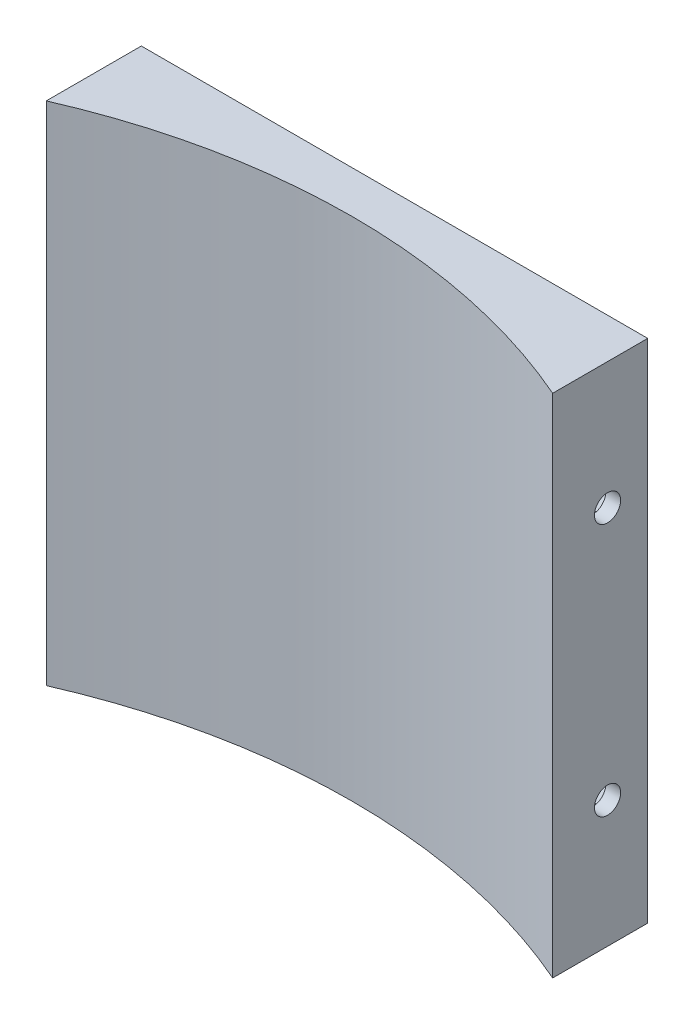
SolidWorks part; units mm, degrees
ref_plane "Plano frontal" through (0, 0, 0) normal (0, 0, 1) x (1, 0, 0)
ref_plane "Plano superior" through (0, 0, 0) normal (0, 1, 0) x (1, 0, 0)
ref_plane "Plano direito" through (0, 0, 0) normal (1, 0, 0) x (0, 0, -1)
sketch "Esboço2" plane through (0, 0, 0) normal (0, 1, 0) x (1, 0, 0)
  line L0 (-60, 0) -> (60, 0)
  line L1 (-60, -22.5227) -> (-60, 0)
  line L2 (60, 0) -> (60, -22.5227)
  arc A0 (-60, -22.5227) -> (60, -22.5227) centre (0, -160) cw
  point P4 (0, 0)
  point P8 (0, -10)
  dimension "D2" = 150
  dimension "D1" = 120
  dimension "D3" = 10
extrude "Ressalto-extrusão1" add sketch "Esboço2" along normal mid plane 120
shell "Casca1" thickness 3.5 removed face at (0, 0, 0)
ref_plane "Plano1" through (0, 0, 0) normal (0, 0, -1) x (-1, 0, 0)
sketch "Esboço7" plane through (0, 0, 0) normal (0, 0, -1) x (-1, 0, 0)
  line L5 (-56.5, -56.5) -> (56.5, -56.5)
  line L6 (-56.5, -56.5) -> (-56.5, 56.5)
  line L11 (-56.5, 56.5) -> (56.5, 56.5)
  line L12 (56.5, -56.5) -> (56.5, 56.5)
  line L13 (-56.5, -56.5) -> (56.5, 56.5) construction
  line L14 (-56.5, 56.5) -> (56.5, -56.5) construction
  line L15 (-52, -52) -> (52, -52)
  line L16 (-52, -52) -> (-52, 52)
  line L17 (-52, 52) -> (52, 52)
  line L18 (52, -52) -> (52, 52)
  line L19 (-52, -52) -> (52, 52) construction
  line L20 (-52, 52) -> (52, -52) construction
  point P0 (0, 0)
  point P5 (0, 0)
  dimension "D1" = 113
  dimension "D2" = 104
  dimension "D3" = 104
extrude "Ressalto-extrusão3" add sketch "Esboço7" along normal mid plane 6 separate body
chamfer "Chanfro1" distance 1 angle 45 4 edges at (56.5, 0, -3) (0, -56.5, -3) (-56.5, 0, -3) (0, 56.5, -3)
sketch "Esboço3" plane through (0, 0, 0) normal (0, 0, -1) x (-1, 0, 0)
  line L0 (-46.5, 51.5) -> (-46.5, 56.5)
  line L1 (-56.5, 56.5) -> (56.5, 56.5) construction
  line L2 (-56.5, 56.5) -> (-56.5, -56.5) construction
  line L3 (-56.5, 56.5) -> (56.5, 56.5) construction
  line L4 (-46.5, 56.5) -> (-56.5, 56.5)
  line L5 (-51.5, 46.5) -> (-56.5, 46.5)
  line L6 (-56.5, 56.5) -> (-56.5, -56.5) construction
  line L7 (-56.5, 46.5) -> (-56.5, 56.5)
  line L8 (0, 12.3875) -> (0, -12.3875) construction
  line L9 (56.5, 46.5) -> (56.5, 56.5)
  line L10 (51.5, 46.5) -> (56.5, 46.5)
  line L11 (46.5, 56.5) -> (56.5, 56.5)
  line L12 (46.5, 51.5) -> (46.5, 56.5)
  line L13 (12.3875, 0) -> (-12.3875, 0) construction
  line L14 (46.5, -51.5) -> (46.5, -56.5)
  line L15 (46.5, -56.5) -> (56.5, -56.5)
  line L16 (51.5, -46.5) -> (56.5, -46.5)
  line L17 (56.5, -46.5) -> (56.5, -56.5)
  line L18 (-56.5, -46.5) -> (-56.5, -56.5)
  line L19 (-51.5, -46.5) -> (-56.5, -46.5)
  line L20 (-46.5, -56.5) -> (-56.5, -56.5)
  line L21 (-46.5, -51.5) -> (-46.5, -56.5)
  line L22 (-51.5, 5) -> (-56.5, 5)
  line L23 (-56.5, 5) -> (-56.5, -5)
  line L24 (-56.5, -5) -> (-51.5, -5)
  line L25 (56.5, -5) -> (51.5, -5)
  line L26 (56.5, 5) -> (56.5, -5)
  line L27 (51.5, 5) -> (56.5, 5)
  line L28 (-5, 51.5) -> (-5, 56.5)
  line L29 (5, 51.5) -> (5, 56.5)
  line L30 (5, 56.5) -> (-5, 56.5)
  line L31 (5, -56.5) -> (-5, -56.5)
  line L32 (5, -51.5) -> (5, -56.5)
  line L33 (-5, -51.5) -> (-5, -56.5)
  arc A0 (-51.5, 46.5) -> (-46.5, 51.5) centre (-51.5, 51.5) ccw
  arc A1 (51.5, 46.5) -> (46.5, 51.5) centre (51.5, 51.5) cw
  arc A2 (51.5, -46.5) -> (46.5, -51.5) centre (51.5, -51.5) ccw
  arc A3 (-51.5, -46.5) -> (-46.5, -51.5) centre (-51.5, -51.5) cw
  arc A4 (-51.5, -5) -> (-51.5, 5) centre (-51.5, 0) ccw
  arc A5 (51.5, -5) -> (51.5, 5) centre (51.5, 0) cw
  arc A6 (-5, 51.5) -> (5, 51.5) centre (0, 51.5) ccw
  arc A7 (-5, -51.5) -> (5, -51.5) centre (0, -51.5) cw
  dimension "D1" = 10
  dimension "D2" = 10
  dimension "D3" = 10
extrude "Ressalto-extrusão2" add sketch "Esboço3" against normal through all
sketch "Esboço4" plane through (0, 0, 0) normal (0, 1, 0) x (1, 0, 0)
  line L0 (-60, -22.5227) -> (-60, -33.5643)
  line L1 (-60, -33.5643) -> (60, -33.5643)
  line L2 (60, -33.5643) -> (60, -22.5227)
  arc A0 (-60, -22.5227) -> (60, -22.5227) centre (0, -160) cw
extrude "Corte-extrusão1" cut sketch "Esboço4" against normal through all both and the other way through all
sketch "Esboço8" plane through (0, 0, 0) normal (0, 0, 1) x (1, 0, 0)
  line L0 (-46.5, 51.5) -> (-46.5, 56.5)
  line L4 (-46.5, 56.5) -> (-56.5, 56.5)
  line L5 (-51.5, 46.5) -> (-56.5, 46.5)
  line L7 (-56.5, 46.5) -> (-56.5, 56.5)
  line L9 (56.5, 46.5) -> (56.5, 56.5)
  line L10 (51.5, 46.5) -> (56.5, 46.5)
  line L11 (46.5, 56.5) -> (56.5, 56.5)
  line L12 (46.5, 51.5) -> (46.5, 56.5)
  line L14 (46.5, -51.5) -> (46.5, -56.5)
  line L15 (46.5, -56.5) -> (56.5, -56.5)
  line L16 (51.5, -46.5) -> (56.5, -46.5)
  line L17 (56.5, -46.5) -> (56.5, -56.5)
  line L18 (-56.5, -46.5) -> (-56.5, -56.5)
  line L19 (-51.5, -46.5) -> (-56.5, -46.5)
  line L20 (-46.5, -56.5) -> (-56.5, -56.5)
  line L21 (-46.5, -51.5) -> (-46.5, -56.5)
  line L22 (-51.5, 5) -> (-56.5, 5)
  line L23 (-56.5, 5) -> (-56.5, -5)
  line L24 (-56.5, -5) -> (-51.5, -5)
  line L25 (56.5, -5) -> (51.5, -5)
  line L26 (56.5, 5) -> (56.5, -5)
  line L27 (51.5, 5) -> (56.5, 5)
  line L28 (-5, 51.5) -> (-5, 56.5)
  line L29 (5, 51.5) -> (5, 56.5)
  line L30 (5, 56.5) -> (-5, 56.5)
  line L31 (5, -56.5) -> (-5, -56.5)
  line L32 (5, -51.5) -> (5, -56.5)
  line L33 (-5, -51.5) -> (-5, -56.5)
  arc A0 (-51.5, 46.5) -> (-46.5, 51.5) centre (-51.5, 51.5) ccw
  arc A1 (51.5, 46.5) -> (46.5, 51.5) centre (51.5, 51.5) cw
  arc A2 (51.5, -46.5) -> (46.5, -51.5) centre (51.5, -51.5) ccw
  arc A3 (-51.5, -46.5) -> (-46.5, -51.5) centre (-51.5, -51.5) cw
  arc A4 (-51.5, -5) -> (-51.5, 5) centre (-51.5, 0) ccw
  arc A5 (51.5, -5) -> (51.5, 5) centre (51.5, 0) cw
  arc A6 (-5, 51.5) -> (5, 51.5) centre (0, 51.5) ccw
  arc A7 (-5, -51.5) -> (5, -51.5) centre (0, -51.5) cw
  dimension "D1" = 10
  dimension "D2" = 10
  dimension "D3" = 10
extrude "Corte-extrusão2" cut sketch "Esboço8" against normal blind 3
sketch "Esboço9" plane through (-60, 0, 0) normal (-1, 0, 0) x (0, 0, 1)
  line L0 (22.5227, 60) -> (22.5227, -60) construction
  line L1 (0, 60) -> (22.5227, 60) construction
  circle A0 centre (9.5227, 30) radius 3.1
  circle A1 centre (9.5227, -30) radius 3.1
  dimension "D1" = 6.2
  dimension "D2" = 13
  dimension "D5" = 6.2
  dimension "D6" = 13
  dimension "D3" = 30
  dimension "D4" = 60
extrude "Corte-extrusão3" cut sketch "Esboço9" against normal blind 10
mirror "Espelhar1" about plane through (0, 0, 0) normal (1, 0, 0) of "Corte-extrusão3"
sketch "Esboço10" plane through (-56.5, 0, 0) normal (1, 0, 0) x (0, 0, -1)
  line L1 (-3.7204, 30) -> (-6.6215, 35.025)
  line L2 (-6.6215, 35.025) -> (-12.4239, 35.025)
  line L3 (-12.4239, 35.025) -> (-15.3251, 30)
  line L4 (-15.3251, 30) -> (-12.4239, 24.975)
  line L5 (-12.4239, 24.975) -> (-6.6215, 24.975)
  line L6 (-6.6215, 24.975) -> (-3.7204, 30)
  circle A0 centre (-9.5227, 30) radius 5.025 construction
  circle A1 centre (-9.5227, 30) radius 7.5
  dimension "D2" = 15
  dimension "D1" = 10.05
extrude "Ressalto-extrusão4" add sketch "Esboço10" along normal blind 4.5
mirror "Espelhar2" about plane through (0, 0, 0) normal (0, 1, 0) of "Ressalto-extrusão4"
mirror "Espelhar3" about plane through (0, 0, 0) normal (1, 0, 0) of "Espelhar2"
